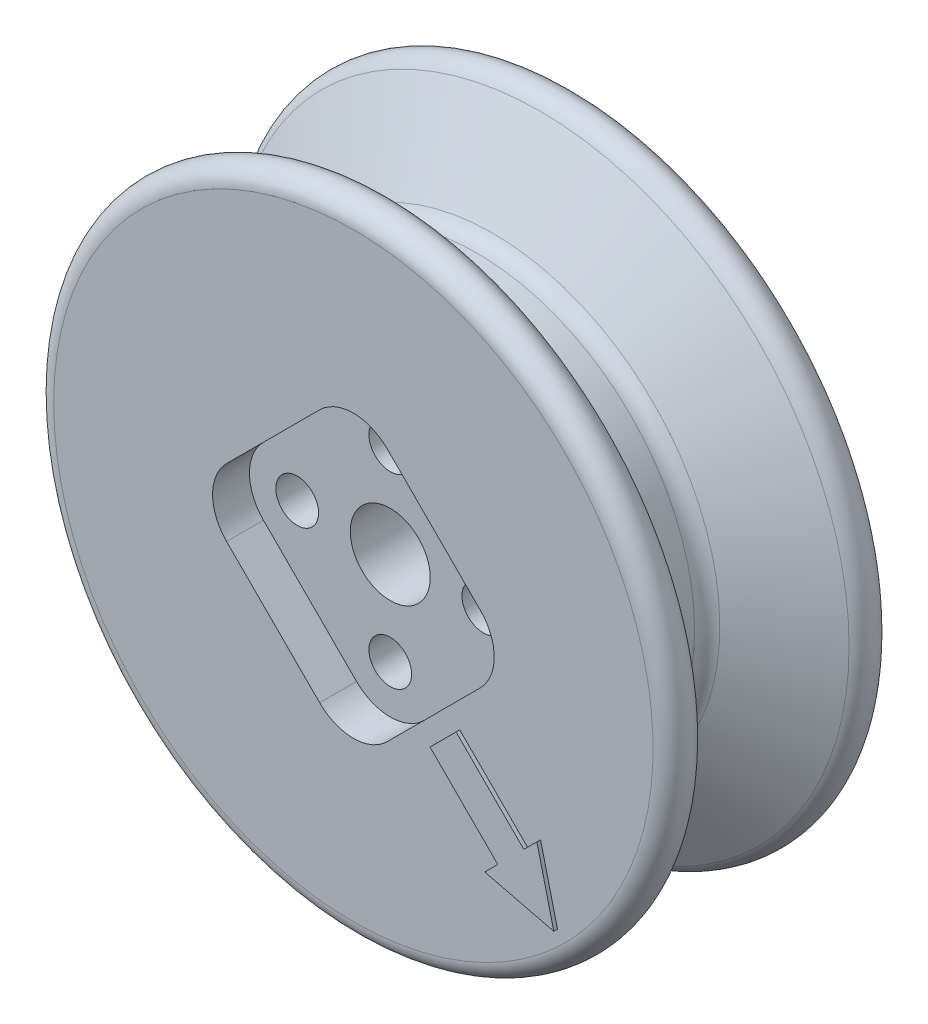
SolidWorks part; units mm, degrees
material "Polymaker PLA"
ref_plane "Front Plane" through (0, 0, 0) normal (0, 0, 1) x (1, 0, 0)
ref_plane "Top Plane" through (0, 0, 0) normal (0, 1, 0) x (1, 0, 0)
ref_plane "Right Plane" through (0, 0, 0) normal (1, 0, 0) x (0, 0, -1)
sketch "Sketch1" plane through (0, 0, 0) normal (0, 0, 1) x (1, 0, 0)
  circle A0 centre (0, 0) radius 2.754
  circle A1 centre (0, 0) radius 9.525
  circle A2 centre (0, 0) radius 9.525
  circle A3 centre (0, 6.4131) radius 1.4732
  circle A4 centre (6.4131, 0) radius 1.4732
  circle A5 centre (0, -6.4131) radius 1.4732
  circle A6 centre (-6.4131, 0) radius 1.4732
  arc A7 (2.4207, -0.6247) -> (0.6247, -2.4207) centre (0, 0) ccw construction
  arc A8 (2.4207, -0.6247) -> (0.6247, -2.4207) centre (0, 0) ccw construction
  point P7 (0, 6.4131)
  point P18 (0, 0)
  point P19 (0, 6.4131)
  dimension "D2" = 2.9464
  dimension "D4" = 0.254
  dimension "D1" = 0
  dimension "D3" = 4
extrude "Boss-Extrude1" add sketch "Sketch1" along normal blind 10.16
ref_axis "Axis1" through (0, 0, 10.16) along (0, 0, -1)
sketch "Sketch2" plane through (0, 0, 0) normal (0, 1, 0) x (1, 0, 0)
  line L0 (15, -3.429) -> (15, -1.651)
  line L1 (9.906, 0) -> (9.525, 0)
  line L2 (9.906, 0) -> (9.906, 5.08)
  line L3 (9.906, 0) -> (9.906, 5.08)
  line L4 (9.525, 0) -> (-9.525, 0) construction
  line L5 (9.525, -10.16) -> (9.525, 0) construction
  line L6 (9.525, 0) -> (9.525, -10.16)
  line L7 (-9.525, -10.16) -> (9.525, -10.16) construction
  line L8 (9.525, -10.16) -> (20.6487, -10.16)
  line L9 (0, 5.08) -> (0, -10.16) construction
  line L10 (15, 5.08) -> (15, -10.16) construction
  line L11 (0, -2.54) -> (15, -2.54) construction
  line L12 (21.2837, -7.7901) -> (15.635, -4.5289)
  line L13 (21.2837, 2.7101) -> (15.635, -0.5511)
  line L14 (9.906, 5.08) -> (20.6487, 5.08)
  arc A0 (15.635, -4.5289) -> (15, -3.429) centre (16.27, -3.429) cw
  arc A1 (15.635, -0.5511) -> (15, -1.651) centre (16.27, -1.651) ccw
  arc A2 (20.6487, -10.16) -> (21.2837, -7.7901) centre (20.6487, -8.89) ccw
  arc A3 (21.2837, 2.7101) -> (20.6487, 5.08) centre (20.6487, 3.81) ccw
  point P32 (15, -2.54)
  point P33 (25.3884, -10.16)
  point P36 (25.3884, 5.08)
  dimension "D3" = 1.27
  dimension "D6" = 1.27
  dimension "D2" = 15
  dimension "D4" = 30
  dimension "D5" = 1.778
  dimension "D1" = 0.381
revolve "Revolve1" add sketch "Sketch2" angle 360 about L9
sketch "Sketch4" plane through (9.1698, -9.1698, 0) normal (-0.7071, 0.7071, 0) x (0, 0, 1)
  circle A0 centre (2.54, 0) radius 2.7813 construction
  circle A1 centre (2.54, 0) radius 2.7813 construction
  circle A2 centre (2.54, 0) radius 3.0353
  circle A3 centre (2.54, 0) radius 1.397
  dimension "D2" = 2.794
  dimension "D1" = 0.254
extrude "Cut-Extrude1" cut sketch "Sketch4" against normal blind 5.08 contours A2
extrude "Cut-Extrude2" cut sketch "Sketch4<3>" along normal up to next contours A3
sketch "Sketch4<3>" plane through (9.1698, -9.1698, 0) normal (-0.7071, 0.7071, 0) x (0, 0, 1) same geometry as "Sketch4"
sketch "Sketch5" plane through (0, 0, 7.62) normal (0, 0, -1) x (-1, 0, 0)
  line L0 (8.739, 2.3259) -> (2.3259, 8.739)
  line L1 (-2.3259, 8.739) -> (-8.739, 2.3259)
  line L2 (-8.739, -2.3259) -> (-2.3259, -8.739)
  line L3 (2.3259, -8.739) -> (8.739, -2.3259)
  circle A0 centre (0, 6.4131) radius 2.7813 construction
  circle A1 centre (0, 6.4131) radius 2.7813 construction
  arc A2 (2.3259, 8.739) -> (-2.3259, 8.739) centre (0, 6.4131) ccw
  arc A3 (8.739, -2.3259) -> (8.739, 2.3259) centre (6.4131, 0) ccw
  arc A4 (-2.3259, -8.739) -> (2.3259, -8.739) centre (0, -6.4131) ccw
  arc A5 (-8.739, 2.3259) -> (-8.739, -2.3259) centre (-6.4131, 0) ccw
  circle A6 centre (0, 6.4131) radius 3.2893 construction
  point P14 (0, 0)
  dimension "D1" = 0.508
  dimension "D2" = 4
extrude "Cut-Extrude3" cut sketch "Sketch5" against normal through all
sketch "Sketch6" plane through (0, 0, 10.16) normal (0, 0, 1) x (1, 0, 0)
  line L0 (0, 0) -> (14.6009, -14.6009) construction
  line L1 (8.739, -2.3259) -> (2.3259, -8.739) construction
  line L2 (10.1576, -8.1819) -> (8.1819, -10.1576) construction
  line L3 (10.1576, -8.1819) -> (8.1819, -10.1576) construction
  line L4 (5.5324, -7.3285) -> (7.3285, -5.5324)
  line L5 (7.3285, -5.5324) -> (11.9982, -10.2022)
  line L6 (11.9982, -10.2022) -> (12.8962, -9.3041)
  line L7 (12.8962, -9.3041) -> (14.062, -14.062)
  line L8 (9.3041, -12.8962) -> (14.062, -14.062)
  line L9 (10.2022, -11.9982) -> (9.3041, -12.8962)
  line L10 (5.5324, -7.3285) -> (10.2022, -11.9982)
  circle A0 centre (0, 0) radius 20.6487 construction
  point P7 (9.1698, -9.1698)
  point P17 (6.4304, -6.4304)
  dimension "D1" = 2.54
  dimension "D2" = 1.27
  dimension "D3" = 1.27
  dimension "D4" = 0.762
  dimension "D5" = 6.604
extrude "Boss-Extrude2" add sketch "Sketch6" along normal blind 0.254
ref_plane "MID_PLANE" through (0, 0, 2.54) normal (0, 0, 1) x (1, 0, 0)
equation "\"pulleyRadius\"=0.590551"
equation "\"D2@Sketch2\"=\"pulleyRadius\""
equation "\"baseWidth\"=0.07"
equation "\"D5@Sketch2\"=\"baseWidth\""
